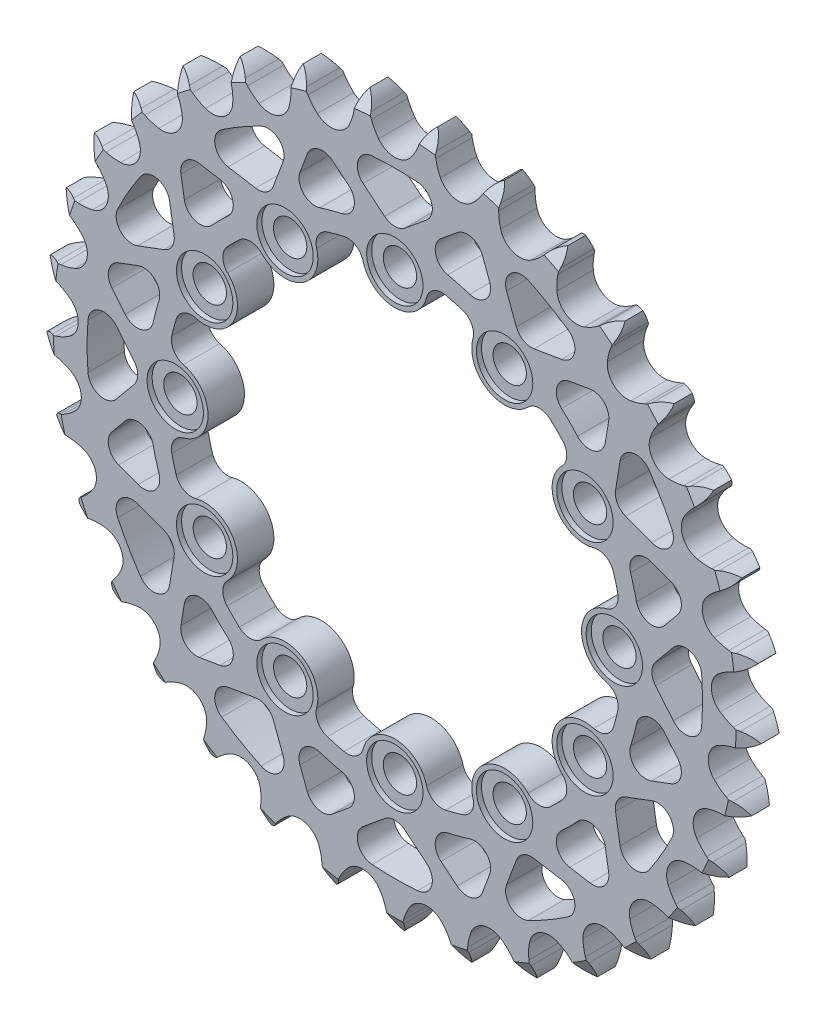
SolidWorks part; units mm, degrees
note: '?' marks a value the reader was unsure of. The reader was unsure of these and kept them because the rebuilt part matched: shared geometry of "Sketch12<3>".
material "7075-T6 (SN)"
ref_plane "Front Plane" through (0, 0, 0) normal (0, 0, 1) x (1, 0, 0)
ref_plane "Top Plane" through (0, 0, 0) normal (0, 1, 0) x (1, 0, 0)
ref_plane "Right Plane" through (0, 0, 0) normal (1, 0, 0) x (0, 0, -1)
sketch "Work Sketch" plane through (0, 0, 0) normal (0, 0, 1) x (1, 0, 0)
  line L0 (0, 0) -> (0, 160.4542) construction
  line L1 (-112.0919, 66.8027) -> (87.2579, 66.8027) construction
  line L2 (5.0834, 120.8822) -> (5.0834, 112.9699) construction
  line L3 (-12.8497, 70.6081) -> (16.7256, 70.6081) construction
  line L4 (5.0834, 70.6081) -> (-6.0658, 62.2619) construction
  line L5 (5.0834, 70.6081) -> (-4.6352, 66.9715) construction
  line L6 (-4.6352, 66.9715) -> (-6.998, 73.2861)
  line L7 (-11.5114, 65.7464) -> (-7.1525, 65.7464) construction
  line L8 (-11.0622, 124.7602) -> (-11.0622, 110.2345) construction
  line L9 (0, 0) -> (-4.0639, 42.5596) construction
  circle A0 centre (0, 0) radius 66.8027
  circle A1 centre (0, 66.8027) radius 4.0088
  arc A2 (-4.6352, 66.9715) -> (-3.2092, 64.4003) centre (5.0609, 70.6677) ccw
  circle A3 centre (-11.0622, 65.7464) radius 6.4488
  point P23 (-3.2092, 64.4003)
  dimension "D1" = 133.6054
  dimension "D8" = 10.3767
  dimension "D2" = 8.0177
  dimension "D3" = 5.0834
  dimension "D4" = 3.8054
  dimension "D5" = 36.818
  dimension "D6" = 16.303
  dimension "D7" = 10.3767
  dimension "D9" = 1.0563
  dimension "D10" = 11.0622
  dimension "D11" = 5.455
sketch "Teeth Sketch" plane through (0, 0, 0) normal (0, 0, 1) x (1, 0, 0)
  line L0 (5.0224, 68.0064) -> (4.6352, 66.9715)
  line L1 (-8.8439, 92.6176) -> (-5.6513, 59.1829) construction
  line L2 (0, 0) -> (-12.8498, 132.1321) construction
  line L3 (7.9387, 67.7279) -> (8.123, 66.6385)
  line L4 (19011.2087, -199094.3845) -> (-19015.2726, 199136.9441) construction
  line L5 (0, 146.3285) -> (0, 56.9858) construction
  line L6 (17.8019, 65.8269) -> (17.2258, 64.8841)
  line L7 (0, -200000) -> (0, 200160.4542) construction
  line L8 (20.6128, 65.0016) -> (20.5877, 63.897)
  line L9 (-4.6352, 66.9715) -> (-6.998, 73.2861) construction
  line L10 (43.2949, 52.6844) -> (42.861, 51.6682)
  line L11 (-5.0224, 68.0064) -> (-4.6352, 66.9715)
  line L12 (29.938, 61.2683) -> (29.1939, 60.4515)
  line L13 (32.5419, 59.9259) -> (32.3082, 58.846)
  line L14 (40.9921, 54.4953) -> (40.1069, 53.8341)
  line L15 (50.5647, 45.7527) -> (49.5703, 45.271)
  line L16 (52.4831, 43.5387) -> (51.8648, 42.623)
  line L17 (58.3096, 35.3565) -> (57.2421, 35.0716)
  line L18 (59.7744, 32.8194) -> (58.9939, 32.0373)
  line L19 (63.9472, 23.6824) -> (62.845, 23.6047)
  line L20 (64.9053, 20.9139) -> (63.9909, 20.2936)
  line L21 (67.2735, 11.1523) -> (66.1765, 11.2846)
  line L22 (67.6904, 8.2526) -> (66.6751, 7.8165)
  line L23 (68.1683, -1.7808) -> (67.1162, -1.4433)
  line L24 (68.0289, -4.7071) -> (66.9495, -4.9431)
  line L25 (66.5994, -14.6496) -> (65.6302, -14.119)
  line L26 (65.9088, -17.4966) -> (64.8042, -17.524)
  line L27 (62.6234, -26.9889) -> (61.7722, -26.2845)
  line L28 (61.4065, -29.6537) -> (60.3166, -29.4716)
  line L29 (56.3841, -38.3527) -> (55.6815, -37.4999)
  line L30 (54.6848, -40.739) -> (53.6491, -40.354)
  line L31 (48.1068, -48.3304) -> (47.5783, -47.3601)
  line L32 (45.9866, -50.352) -> (45.0425, -49.7779)
  line L33 (38.0909, -56.5613) -> (37.7556, -55.5085)
  line L34 (35.6264, -58.1451) -> (34.808, -57.4027)
  line L35 (26.6983, -62.7479) -> (26.5682, -61.6506)
  line L36 (23.9786, -63.8367) -> (23.3155, -62.9529)
  line L37 (14.3407, -66.6666) -> (14.4207, -65.5646)
  line L38 (11.4641, -67.221) -> (10.9802, -66.2277)
  line L39 (1.4648, -68.1759) -> (1.7519, -67.1089)
  line L40 (-1.4648, -68.1759) -> (-1.7519, -67.1089)
  line L41 (-11.4641, -67.221) -> (-10.9802, -66.2277)
  line L42 (-14.3407, -66.6666) -> (-14.4207, -65.5646)
  line L43 (-23.9786, -63.8367) -> (-23.3155, -62.9529)
  line L44 (-26.6983, -62.7479) -> (-26.5682, -61.6506)
  line L45 (-35.6264, -58.1451) -> (-34.808, -57.4027)
  line L46 (-38.0909, -56.5613) -> (-37.7556, -55.5085)
  line L47 (-45.9866, -50.352) -> (-45.0425, -49.7779)
  line L48 (-48.1068, -48.3304) -> (-47.5783, -47.3601)
  line L49 (-54.6848, -40.739) -> (-53.6491, -40.354)
  line L50 (-56.3841, -38.3527) -> (-55.6815, -37.4999)
  line L51 (-61.4065, -29.6537) -> (-60.3166, -29.4716)
  line L52 (-62.6234, -26.9889) -> (-61.7722, -26.2845)
  line L53 (-65.9088, -17.4966) -> (-64.8042, -17.524)
  line L54 (-66.5994, -14.6496) -> (-65.6302, -14.119)
  line L55 (-68.0289, -4.7071) -> (-66.9495, -4.9431)
  line L56 (-68.1683, -1.7808) -> (-67.1162, -1.4433)
  line L57 (-67.6904, 8.2526) -> (-66.6751, 7.8165)
  line L58 (-67.2735, 11.1523) -> (-66.1765, 11.2846)
  line L59 (-64.9053, 20.9139) -> (-63.9909, 20.2936)
  line L60 (-63.9472, 23.6824) -> (-62.845, 23.6047)
  line L61 (-59.7744, 32.8194) -> (-58.9939, 32.0373)
  line L62 (-58.3096, 35.3565) -> (-57.2421, 35.0716)
  line L63 (-52.4831, 43.5387) -> (-51.8648, 42.623)
  line L64 (-50.5647, 45.7527) -> (-49.5703, 45.271)
  line L65 (-43.2949, 52.6844) -> (-42.861, 51.6682)
  line L66 (-40.9921, 54.4953) -> (-40.1069, 53.8341)
  line L67 (-32.5419, 59.9259) -> (-32.3082, 58.846)
  line L68 (-29.938, 61.2683) -> (-29.1939, 60.4515)
  line L69 (-20.6128, 65.0016) -> (-20.5877, 63.897)
  line L70 (-17.8019, 65.8269) -> (-17.2258, 64.8841)
  line L71 (-7.9387, 67.7279) -> (-8.123, 66.6385)
  arc A0 (-6.8704, 70.647) -> (-5.0224, 68.0064) centre (-11.0622, 65.7464) cw
  circle A1 centre (-11.0622, 65.7464) radius 6.4488 construction
  arc A2 (-3.2092, 64.4003) -> (-4.6352, 66.9715) centre (5.0609, 70.6677) cw
  arc A3 (-4.6352, 66.9715) -> (-3.2092, 64.4003) centre (5.0609, 70.6677) ccw construction
  circle A4 centre (0, 66.8027) radius 4.0088 construction
  arc A5 (-3.2092, 64.4003) -> (3.2092, 64.4003) centre (0, 66.8027) ccw
  arc A6 (3.2092, 64.4003) -> (4.6352, 66.9715) centre (-5.0609, 70.6677) ccw
  arc A7 (6.8704, 70.647) -> (5.0224, 68.0064) centre (11.0622, 65.7464) ccw
  arc A8 (6.6238, 70.6705) -> (7.9387, 67.7279) centre (1.5803, 66.6518) cw
  arc A9 (9.0366, 63.8438) -> (8.123, 66.6385) centre (18.3434, 68.4328) cw
  arc A10 (9.0366, 63.8438) -> (15.3391, 62.6291) centre (12.6425, 65.5955) ccw
  arc A11 (15.3391, 62.6291) -> (17.2258, 64.8841) centre (8.4044, 70.3484) ccw
  arc A12 (20.1163, 68.0701) -> (17.8019, 65.8269) centre (23.3049, 62.4647) ccw
  arc A13 (19.8786, 68.1399) -> (20.6128, 65.0016) centre (14.1657, 65.1482) cw
  arc A14 (20.9558, 60.9799) -> (20.5877, 63.897) centre (30.9629, 63.7246) cw
  arc A15 (20.9558, 60.9799) -> (26.9145, 58.5944) centre (24.8281, 62.0175) ccw
  arc A16 (26.9145, 58.5944) -> (29.1939, 60.4515) centre (21.5661, 67.4865) ccw
  arc A17 (32.6351, 63.0329) -> (29.938, 61.2683) centre (34.7052, 56.9254) ccw
  arc A18 (32.4149, 63.1465) -> (32.5419, 59.9259) centre (26.2391, 61.29) cw
  arc A19 (32.1176, 55.912) -> (32.3082, 58.846) centre (42.4634, 56.7133) cw
  arc A20 (32.1176, 55.912) -> (37.5172, 52.4419) centre (36.1163, 56.198) ccw
  arc A21 (37.5172, 52.4419) -> (40.1069, 53.8341) centre (33.9483, 62.1856) ccw
  arc A22 (43.9744, 55.7176) -> (40.9921, 54.4953) centre (44.8513, 49.3287) ccw
  arc A23 (43.7796, 55.8708) -> (43.2949, 52.6844) centre (37.3641, 55.2167) cw
  arc A24 (42.1187, 48.8233) -> (42.861, 51.6682) centre (52.429, 47.6521) cw
  arc A25 (42.1187, 48.8233) -> (46.7639, 44.3941) centre (46.0991, 48.3474) ccw
  arc A26 (46.7639, 44.3941) -> (49.5703, 45.271) centre (45.1035, 54.637) ccw
  arc A27 (53.7244, 46.3885) -> (50.5647, 45.7527) centre (53.3763, 39.9491) ccw
  arc A28 (53.5621, 46.5757) -> (52.4831, 43.5387) centre (47.1387, 47.1476) cw
  arc A29 (50.5974, 39.97) -> (51.8648, 42.623) centre (60.4998, 36.8687) cw
  arc A30 (50.5974, 39.97) -> (54.3205, 34.7417) centre (54.4159, 38.7494) ccw
  arc A31 (54.3205, 34.7417) -> (57.2421, 35.0716) centre (54.6285, 45.1138) ccw
  arc A32 (61.5326, 35.3828) -> (58.3096, 35.3565) centre (59.9721, 29.1257) ccw
  arc A33 (61.4087, 35.5974) -> (59.7744, 32.8194) centre (55.2096, 37.3746) cw
  arc A34 (57.2474, 29.6721) -> (58.9939, 32.0373) centre (66.384, 24.7528) cw
  arc A35 (57.2474, 29.6721) -> (59.9137, 23.8336) centre (60.7659, 27.7508) ccw
  arc A36 (59.9137, 23.8336) -> (62.845, 23.6047) centre (62.1792, 33.96) ccw
  arc A37 (67.1168, 23.0983) -> (63.9472, 23.6824) centre (64.4004, 17.2495) ccw
  arc A38 (67.0358, 23.3324) -> (64.9053, 20.9139) centre (61.2851, 26.2507) cw
  arc A39 (61.8283, 18.3017) -> (63.9909, 20.2936) centre (69.8688, 11.7422) cw
  arc A40 (61.8283, 18.3017) -> (63.3416, 12.0642) centre (64.9196, 15.7493) ccw
  arc A41 (63.3416, 12.0642) -> (66.1765, 11.2846) centre (67.4825, 21.5788) ccw
  arc A42 (70.2753, 9.9789) -> (67.2735, 11.1523) centre (66.5011, 4.7499) ccw
  arc A43 (70.2401, 10.2242) -> (67.6904, 8.2526) centre (65.1456, 14.178) cw
  arc A44 (64.1746, 6.2699) -> (66.6751, 7.8165) centre (70.8284, -1.6927) cw
  arc A45 (64.1746, 6.2699) -> (64.48, -0.1413) centre (66.727, 3.1786) ccw
  arc A46 (64.48, -0.1413) -> (67.1162, -1.4433) centre (70.3468, 8.4177) ccw
  arc A47 (70.8939, -3.5011) -> (68.1683, -1.7808) centre (66.1983, -7.9213) ccw
  arc A48 (70.9057, -3.2536) -> (68.0289, -4.7071) centre (66.6515, 1.5929) cw
  arc A49 (64.2015, -5.9885) -> (66.9495, -4.9431) centre (69.2281, -15.0665) cw
  arc A50 (64.2015, -5.9885) -> (63.2881, -12.3417) centre (66.1227, -9.507) ccw
  arc A51 (63.2881, -12.3417) -> (65.6302, -14.119) centre (70.6686, -5.0476) ccw
  arc A52 (68.9501, -16.8546) -> (66.5994, -14.6496) centre (63.5029, -20.3063) ccw
  arc A53 (69.0085, -16.6138) -> (65.9088, -17.4966) centre (65.7485, -11.0498) cw
  arc A54 (61.908, -18.0305) -> (64.8042, -17.524) centre (65.1257, -27.8957) cw
  arc A55 (61.908, -18.0305) -> (59.8087, -24.096) centre (63.1286, -21.849) ccw
  arc A56 (59.8087, -24.096) -> (61.7722, -26.2845) centre (68.4363, -18.3305) ccw
  arc A57 (64.5144, -29.5989) -> (62.6234, -26.9889) centre (58.5123, -31.9573) ccw
  arc A58 (64.6173, -29.3735) -> (61.4065, -29.6537) centre (62.4691, -23.2931) cw
  arc A59 (57.3769, -29.4209) -> (60.3166, -29.4716) centre (58.6695, -39.7167) cw
  arc A60 (57.3769, -29.4209) -> (54.1677, -34.9794) centre (57.8528, -33.4013) ccw
  arc A61 (54.1677, -34.9794) -> (55.6815, -37.4999) centre (63.7305, -30.9509) ccw
  arc A62 (57.7469, -41.2734) -> (56.3841, -38.3527) centre (51.4069, -42.4533) ccw
  arc A63 (57.8906, -41.0716) -> (54.6848, -40.739) centre (56.932, -34.6945) cw
  arc A64 (50.7721, -39.7478) -> (53.6491, -40.354) centre (50.0928, -50.1023) cw
  arc A65 (50.7721, -39.7478) -> (46.5689, -44.5986) centre (50.4861, -43.7465) ccw
  arc A66 (46.5689, -44.5986) -> (47.5783, -47.3601) centre (56.7213, -42.4527) ccw
  arc A67 (48.8923, -51.4562) -> (48.1068, -48.3304) centre (42.4436, -51.415) ccw
  arc A68 (49.0716, -51.2853) -> (45.9866, -50.352) centre (49.3372, -44.842) cw
  arc A69 (42.3322, -48.6382) -> (45.0425, -49.7779) centre (39.7057, -58.677) cw
  arc A70 (42.3322, -48.6382) -> (37.287, -52.6059) centre (41.2947, -52.5105) ccw
  arc A71 (37.287, -52.6059) -> (37.7556, -55.5085) centre (47.662, -52.4201) ccw
  arc A72 (38.2706, -59.7793) -> (38.0909, -56.5613) centre (31.9463, -58.5183) ccw
  arc A73 (38.479, -59.6453) -> (35.6264, -58.1451) centre (39.9592, -53.3687) cw
  arc A74 (32.3624, -55.7707) -> (34.808, -57.4027) centre (27.8834, -65.131) cw
  arc A75 (32.3624, -55.7707) -> (26.6574, -58.7118) centre (30.6108, -59.3766) ccw
  arc A76 (26.6574, -58.7118) -> (26.5682, -61.6506) centre (36.8801, -60.4929) ccw
  arc A77 (26.2657, -65.9417) -> (26.6983, -62.7479) centre (20.2943, -63.5067) ccw
  arc A78 (26.4957, -65.8497) -> (23.9786, -63.8367) centre (29.137, -59.9666) cw
  arc A79 (21.2229, -60.8875) -> (23.3155, -62.9529) centre (15.0534, -69.2309) cw
  arc A80 (21.2229, -60.8875) -> (15.0644, -62.6958) centre (18.8205, -64.0967) ccw
  arc A81 (15.0644, -62.6958) -> (14.4207, -65.5646) centre (24.7653, -66.3793) ccw
  arc A82 (13.3114, -69.7209) -> (14.3407, -66.6666) centre (7.9088, -66.1998) ccw
  arc A83 (13.5547, -69.674) -> (11.4641, -67.221) centre (17.2617, -64.3972) cw
  arc A84 (9.3163, -63.8036) -> (10.9802, -66.2277) centre (1.6794, -70.8287) cw
  arc A85 (9.3163, -63.8036) -> (2.9269, -64.4137) centre (6.35, -66.5002) ccw
  arc A86 (2.9269, -64.4137) -> (1.7519, -67.1089) centre (11.7554, -69.8666) ccw
  arc A87 (-0.1239, -70.9802) -> (1.4648, -68.1759) centre (-4.7625, -66.5002) ccw
  arc A88 (0.1239, -70.9802) -> (-1.4648, -68.1759) centre (4.7625, -66.5002) cw
  arc A89 (-2.9269, -64.4137) -> (-1.7519, -67.1089) centre (-11.7554, -69.8666) cw
  arc A90 (-2.9269, -64.4137) -> (-9.3163, -63.8036) centre (-6.35, -66.5002) ccw
  arc A91 (-9.3163, -63.8036) -> (-10.9802, -66.2277) centre (-1.6794, -70.8287) ccw
  arc A92 (-13.5547, -69.674) -> (-11.4641, -67.221) centre (-17.2617, -64.3972) ccw
  arc A93 (-13.3114, -69.7209) -> (-14.3407, -66.6666) centre (-7.9088, -66.1998) cw
  arc A94 (-15.0644, -62.6958) -> (-14.4207, -65.5646) centre (-24.7653, -66.3793) cw
  arc A95 (-15.0644, -62.6958) -> (-21.2229, -60.8875) centre (-18.8205, -64.0967) ccw
  arc A96 (-21.2229, -60.8875) -> (-23.3155, -62.9529) centre (-15.0534, -69.2309) ccw
  arc A97 (-26.4957, -65.8497) -> (-23.9786, -63.8367) centre (-29.137, -59.9666) ccw
  arc A98 (-26.2657, -65.9417) -> (-26.6983, -62.7479) centre (-20.2943, -63.5067) cw
  arc A99 (-26.6574, -58.7118) -> (-26.5682, -61.6506) centre (-36.8801, -60.4929) cw
  arc A100 (-26.6574, -58.7118) -> (-32.3624, -55.7707) centre (-30.6108, -59.3766) ccw
  arc A101 (-32.3624, -55.7707) -> (-34.808, -57.4027) centre (-27.8834, -65.131) ccw
  arc A102 (-38.479, -59.6453) -> (-35.6264, -58.1451) centre (-39.9592, -53.3687) ccw
  arc A103 (-38.2706, -59.7793) -> (-38.0909, -56.5613) centre (-31.9463, -58.5183) cw
  arc A104 (-37.287, -52.6059) -> (-37.7556, -55.5085) centre (-47.662, -52.4201) cw
  arc A105 (-37.287, -52.6059) -> (-42.3322, -48.6382) centre (-41.2947, -52.5105) ccw
  arc A106 (-42.3322, -48.6382) -> (-45.0425, -49.7779) centre (-39.7057, -58.677) ccw
  arc A107 (-49.0716, -51.2853) -> (-45.9866, -50.352) centre (-49.3372, -44.842) ccw
  arc A108 (-48.8923, -51.4562) -> (-48.1068, -48.3304) centre (-42.4436, -51.415) cw
  arc A109 (-46.5689, -44.5986) -> (-47.5783, -47.3601) centre (-56.7213, -42.4527) cw
  arc A110 (-46.5689, -44.5986) -> (-50.7721, -39.7478) centre (-50.4861, -43.7465) ccw
  arc A111 (-50.7721, -39.7478) -> (-53.6491, -40.354) centre (-50.0928, -50.1023) ccw
  arc A112 (-57.8906, -41.0716) -> (-54.6848, -40.739) centre (-56.932, -34.6945) ccw
  arc A113 (-57.7469, -41.2734) -> (-56.3841, -38.3527) centre (-51.4069, -42.4533) cw
  arc A114 (-54.1677, -34.9794) -> (-55.6815, -37.4999) centre (-63.7305, -30.9509) cw
  arc A115 (-54.1677, -34.9794) -> (-57.3769, -29.4209) centre (-57.8528, -33.4013) ccw
  arc A116 (-57.3769, -29.4209) -> (-60.3166, -29.4716) centre (-58.6695, -39.7167) ccw
  arc A117 (-64.6173, -29.3735) -> (-61.4065, -29.6537) centre (-62.4691, -23.2931) ccw
  arc A118 (-64.5144, -29.5989) -> (-62.6234, -26.9889) centre (-58.5123, -31.9573) cw
  arc A119 (-59.8087, -24.096) -> (-61.7722, -26.2845) centre (-68.4363, -18.3305) cw
  arc A120 (-59.8087, -24.096) -> (-61.908, -18.0305) centre (-63.1286, -21.849) ccw
  arc A121 (-61.908, -18.0305) -> (-64.8042, -17.524) centre (-65.1257, -27.8957) ccw
  arc A122 (-69.0085, -16.6138) -> (-65.9088, -17.4966) centre (-65.7485, -11.0498) ccw
  arc A123 (-68.9501, -16.8546) -> (-66.5994, -14.6496) centre (-63.5029, -20.3063) cw
  arc A124 (-63.2881, -12.3417) -> (-65.6302, -14.119) centre (-70.6686, -5.0476) cw
  arc A125 (-63.2881, -12.3417) -> (-64.2015, -5.9885) centre (-66.1227, -9.507) ccw
  arc A126 (-64.2015, -5.9885) -> (-66.9495, -4.9431) centre (-69.2281, -15.0665) ccw
  arc A127 (-70.9057, -3.2536) -> (-68.0289, -4.7071) centre (-66.6515, 1.5929) ccw
  arc A128 (-70.8939, -3.5011) -> (-68.1683, -1.7808) centre (-66.1983, -7.9213) cw
  arc A129 (-64.48, -0.1413) -> (-67.1162, -1.4433) centre (-70.3468, 8.4177) cw
  arc A130 (-64.48, -0.1413) -> (-64.1746, 6.2699) centre (-66.727, 3.1786) ccw
  arc A131 (-64.1746, 6.2699) -> (-66.6751, 7.8165) centre (-70.8284, -1.6927) ccw
  arc A132 (-70.2401, 10.2242) -> (-67.6904, 8.2526) centre (-65.1456, 14.178) ccw
  arc A133 (-70.2753, 9.9789) -> (-67.2735, 11.1523) centre (-66.5011, 4.7499) cw
  arc A134 (-63.3416, 12.0642) -> (-66.1765, 11.2846) centre (-67.4825, 21.5788) cw
  arc A135 (-63.3416, 12.0642) -> (-61.8283, 18.3017) centre (-64.9196, 15.7493) ccw
  arc A136 (-61.8283, 18.3017) -> (-63.9909, 20.2936) centre (-69.8688, 11.7422) ccw
  arc A137 (-67.0358, 23.3324) -> (-64.9053, 20.9139) centre (-61.2851, 26.2507) ccw
  arc A138 (-67.1168, 23.0983) -> (-63.9472, 23.6824) centre (-64.4004, 17.2495) cw
  arc A139 (-59.9137, 23.8336) -> (-62.845, 23.6047) centre (-62.1792, 33.96) cw
  arc A140 (-59.9137, 23.8336) -> (-57.2474, 29.6721) centre (-60.7659, 27.7508) ccw
  arc A141 (-57.2474, 29.6721) -> (-58.9939, 32.0373) centre (-66.384, 24.7528) ccw
  arc A142 (-61.4087, 35.5974) -> (-59.7744, 32.8194) centre (-55.2096, 37.3746) ccw
  arc A143 (-61.5326, 35.3828) -> (-58.3096, 35.3565) centre (-59.9721, 29.1257) cw
  arc A144 (-54.3205, 34.7417) -> (-57.2421, 35.0716) centre (-54.6285, 45.1138) cw
  arc A145 (-54.3205, 34.7417) -> (-50.5974, 39.97) centre (-54.4159, 38.7494) ccw
  arc A146 (-50.5974, 39.97) -> (-51.8648, 42.623) centre (-60.4998, 36.8687) ccw
  arc A147 (-53.5621, 46.5757) -> (-52.4831, 43.5387) centre (-47.1387, 47.1476) ccw
  arc A148 (-53.7244, 46.3885) -> (-50.5647, 45.7527) centre (-53.3763, 39.9491) cw
  arc A149 (-46.7639, 44.3941) -> (-49.5703, 45.271) centre (-45.1035, 54.637) cw
  arc A150 (-46.7639, 44.3941) -> (-42.1187, 48.8233) centre (-46.0991, 48.3474) ccw
  arc A151 (-42.1187, 48.8233) -> (-42.861, 51.6682) centre (-52.429, 47.6521) ccw
  arc A152 (-43.7796, 55.8708) -> (-43.2949, 52.6844) centre (-37.3641, 55.2167) ccw
  arc A153 (-43.9744, 55.7176) -> (-40.9921, 54.4953) centre (-44.8513, 49.3287) cw
  arc A154 (-37.5172, 52.4419) -> (-40.1069, 53.8341) centre (-33.9483, 62.1856) cw
  arc A155 (-37.5172, 52.4419) -> (-32.1176, 55.912) centre (-36.1163, 56.198) ccw
  arc A156 (-32.1176, 55.912) -> (-32.3082, 58.846) centre (-42.4634, 56.7133) ccw
  arc A157 (-32.4149, 63.1465) -> (-32.5419, 59.9259) centre (-26.2391, 61.29) ccw
  arc A158 (-32.6351, 63.0329) -> (-29.938, 61.2683) centre (-34.7052, 56.9254) cw
  arc A159 (-26.9145, 58.5944) -> (-29.1939, 60.4515) centre (-21.5661, 67.4865) cw
  arc A160 (-26.9145, 58.5944) -> (-20.9558, 60.9799) centre (-24.8281, 62.0175) ccw
  arc A161 (-20.9558, 60.9799) -> (-20.5877, 63.897) centre (-30.9629, 63.7246) ccw
  arc A162 (-19.8786, 68.1399) -> (-20.6128, 65.0016) centre (-14.1657, 65.1482) ccw
  arc A163 (-20.1163, 68.0701) -> (-17.8019, 65.8269) centre (-23.3049, 62.4647) cw
  arc A164 (-15.3391, 62.6291) -> (-17.2258, 64.8841) centre (-8.4044, 70.3484) cw
  arc A165 (-15.3391, 62.6291) -> (-9.0366, 63.8438) centre (-12.6425, 65.5955) ccw
  arc A166 (-9.0366, 63.8438) -> (-8.123, 66.6385) centre (-18.3434, 68.4328) ccw
  arc A167 (-6.6238, 70.6705) -> (-7.9387, 67.7279) centre (-1.5803, 66.6518) ccw
  point P77 (0, 0)
  dimension "D1" = 5.455
  dimension "D2" = 5.555
  dimension "D3" = 33
extrude "Extrusion" add sketch "Teeth Sketch" along normal blind 7.2136
ref_axis "Axis2" through (0, 0, 38.9715) along (0, 0, -1)?
hole_wizard "M6 Clearance Hole1" positions "Sketch6" profile "Sketch7" hole size "M6" standard "ANSI Metric"
sketch "Sketch6" plane through (0, 0, 0) normal (0, 0, -1) x (-1, 0, 0)
  circle A0 centre (0, 0) radius 43.5
  point P0 (0, 43.5)
  dimension "D1" = 87
sketch "Sketch7" plane through (0, 43.5, 0) normal (1, 0, 0) x (0, 1, 0)
  line L0 (0, 0) -> (0, 19.2548)
  line L1 (0, 19.2548) -> (3.3, 17.272)
  line L2 (3.3, 17.272) -> (3.3, 0)
  line L5 (3.3, 0) -> (0, 0)
  line L10 (0, 19.2548) -> (-3.3, 17.272) construction
  line L11 (0, -6.35) -> (0, 107.95) construction
  dimension "Hole Dia." = 6.6
  dimension "Hole Depth" = 17.272
  dimension "Drill Angle" = 118
pattern_circular "CirPattern1" count 12 over 360 about axis through (0, 0, 0) along (0, 0, 1) of "M6 Clearance Hole1"
sketch "Sketch8" plane through (0, 0, 0) normal (0, 0, -1) x (-1, 0, 0)
  circle A0 centre (0, 0) radius 37
  dimension "D1" = 74
extrude "Cut-Extrude1" cut sketch "Sketch8" against normal through all both and the other way through all
ref_plane "Sprocket Center Plane" through (0, 0, 3.6068) normal (0, 0, 1) x (1, 0, 0)
sketch "Pitch Circle" plane through (0, 0, 3.6068) normal (0, 0, -1) x (-1, 0, 0)
  circle A0 centre (0, 0) radius 66.8027 construction
  dimension "D1" = 133.6054
ref_plane "Center Plane" through (0, 0, 3.6068) normal (0, 0, 1) x (1, 0, 0)
ref_axis "Axis1" through (0, 0, 7.2136) along (0, 0, -1)
sketch "Sketch5" plane through (0, 0, 0) normal (1, 0, 0) x (0, 0, -1)
  line L0 (-1.8288, -70.8482) -> (-5.3848, -70.8482)
  line L1 (-7.2136, -51.2753) -> (0, -51.2753) construction
  line L2 (-5.3848, -70.8482) -> (-5.3848, -67.6547)
  line L3 (-5.3848, -67.6547) -> (-7.2136, -67.6547)
  line L4 (-7.2136, -67.6547) -> (-5.3848, -70.8482)
  line L5 (-7.2136, -67.6547) -> (-7.2136, -70.8482)
  line L6 (-7.2136, -70.8482) -> (-5.3848, -70.8482)
  line L10 (-7.2136, -70.8482) -> (0, -70.8482) construction
  dimension "D1" = 3.556
  dimension "D2" = 3.1936
  dimension "D3" = 1.8288
revolve "Cut-Revolve1" cut sketch "Sketch5" angle 360 about axis through (0, 0, 7.2136) along (0, 0, -1)
mirror "Mirror1" about plane through (0, 0, 3.6068) normal (0, 0, 1) of "Cut-Revolve1"
sketch "Sketch10" plane through (0, 0, 0) normal (0, 0, 1) x (1, 0, 0)
  circle A0 centre (-43.5, 0) radius 5.588
  dimension "D1" = 11.176
extrude "Cut-Extrude2" cut sketch "Sketch10" against normal blind 1.016 from surface at 7.2136 starting at face at (-37, 0, 7.2136)
pattern_circular "CirPattern2" count 12 over 360 about axis through (0, 0, 0) along (0, 0, 1) of "Cut-Extrude2"
ref_plane "Half Plane" through (0, 0, 3.6068) normal (0, 0, 1) x (1, 0, 0)
sketch "Motor Shaft Sprocket Dimensions" plane through (0, 0, 3.6068) normal (0, 0, 1) x (1, 0, 0)
  line L0 (0, 0) -> (-177.8, 0)
  line L1 (-177.8, 0) -> (-177.8, 23.6982)
  line L2 (-180.2273, 51.0991) -> (-5.8945, 66.5421)
  line L3 (-187.3193, -2.1104) -> (-23.1174, -62.6753)
  line L4 (-5.8945, 66.5421) -> (0, 0)
  line L5 (0, 0) -> (-23.1174, -62.6753)
  circle A0 centre (-177.8, 23.6982) radius 27.5082
  circle A1 centre (0, 0) radius 66.8027 construction
  dimension "D3" = 55.0164
  dimension "D1" = 177.8
  dimension "D2" = 23.6982
  dimension "D4" = 205.308
sketch "Sketch12" plane through (0, 0, 0) normal (0, 0, 1) x (1, 0, 0)
  line L0 (-30.8788, 0) -> (49969.1212, 0) construction
  line L1 (-26.8339, 15.4926) -> (43274.4363, -24984.5074) construction
  line L2 (-31.6175, 8.4719) -> (48264.6738, -12932.4804) construction
  line L3 (-58.8828, 15.7776) -> (-48.8851, 3.6402)
  line L4 (-58.8828, 15.7776) -> (-44.1558, 21.29)
  line L5 (-59.7901, 11.8853) -> (-50, 0)
  line L6 (-59.7901, -11.8853) -> (-50, 0)
  line L7 (-44.1558, 21.29) -> (-48.8851, 3.6402) construction
  line L8 (-42.0363, 16.9329) -> (-44.871, 6.3538) construction
  circle A0 centre (-43.5, 0) radius 6.5
  circle A1 centre (0, 0) radius 37 construction
  circle A2 centre (0, 0) radius 60.96 construction
  circle A3 centre (-37.6721, 21.75) radius 6.5
  arc A4 (-37, 0) -> (-32.0429, 18.5) centre (0, 0) cw
  arc A5 (-59.7901, -11.8853) -> (-59.7901, 11.8853) centre (0, 0) cw
  arc A6 (-48.8851, 3.6402) -> (-44.1558, 21.29) centre (0, 0) cw
  arc A7 (-44.871, 6.3538) -> (-42.0363, 16.9329) centre (0, 0) cw
  point P17 (-35.7393, 9.5763)
  point P18 (-58.8828, 15.7776)
  dimension "D1" = 121.92
  dimension "D2" = 3.175
  dimension "D3" = 3.175
extrude "Cut-Extrude3" cut sketch "Sketch12" along normal through all contours A0 A4 A3 L4 L3 | L7 L4 L3
fillet "Fillet1" radius 3.175 5 edges at (-58.8828, 15.7776, 3.6068) (-44.871, 6.3538, 3.6068) (-42.0363, 16.9329, 3.6068) (-48.8851, 3.6402, 3.6068) (-44.1558, 21.29, 3.6068)
extrude "Cut-Extrude4" cut sketch "Sketch12<3>" along normal through all contours A5 L6 L5
sketch "Sketch12<3>" plane through (0, 0, 0) normal (0, 0, 1) x (1, 0, 0) same geometry as "Sketch12"
fillet "Fillet3" radius 3.175 3 edges at (-50, 0, 3.6068) (-59.7901, -11.8853, 3.6068) (-59.7901, 11.8853, 3.6068)
pattern_circular "CirPattern4" count 12 over 360 about axis through (0, 0, 0) along (0, 0, 1) of "Cut-Extrude3", "Cut-Extrude4", "Fillet1", "Fillet3"
equation "\"P\"= 0.500'//Chain Pitch"
equation "\"N\"= 33'//Number of Teeth"
equation "\"Dr\"= 5 / 16'//Roller Diameter"
equation "\"Ds\"= 1.0005 * \"Dr\" + 0.003'Seating Curve DIameter"
equation "\"R\"= \"Ds\" / 2"
equation "\"A\"= 35 + 60 / \"N\""
equation "\"B\"= 18 - 56 / \"N\""
equation "\"ac\"= 0.8 * \"Dr\""
equation "\"M\"= 0.8 * \"Dr\" * cos ( 35 + 60 / \"N\" )"
equation "\"T\"= 0.8 * \"Dr\" * sin ( 35 + 60 / \"N\" )"
equation "\"E\"= 1.3025 * \"Dr\" + 0.0015"
equation "\"Chordal Length of Arc xy\"= ( 2.605 * \"Dr\" + 0.003 ) * sin ( 9 - 28 / \"N\" )"
equation "\"yz\"= \"Dr\" * ( 1.4 * sin ( 17 - 64 / \"N\" ) - 0.8 * sin ( 18 - 56 / \"N\" ) )"
equation "\"ab\"= 1.4 * \"Dr\""
equation "\"W\"= 1.4 * \"Dr\" * cos ( 180 / \"N\" )"
equation "\"V\"= 1.4 * \"Dr\" * sin ( 180 / \"N\" )"
equation "\"F\"= \"Dr\" * ( 0.8 * cos ( 18 - 56 / \"N\" ) + 1.4 * cos ( 17 - 64 / \"N\" ) - 1.3025 )"
equation "\"H\"= sqr ( \"F\" ^ 2 - ( 1.4 * \"Dr\" - \"P\" / 2 ) ^ 2 )"
equation "\"S\"= \"P\" / 2 * cos ( 180 / \"N\" ) + \"H\" * sin ( 180 / \"N\" )"
equation "\"PD\"= \"P\" / ( sin ( 180 / \"N\" ) )"
equation "\"D1@Work Sketch\" = \"PD\""
equation "\"D3@Work Sketch\" = \"M\""
equation "\"D4@Work Sketch\" = \"T\""
equation "\"D5@Work Sketch\" = \"A\""
equation "\"D6@Work Sketch\" = \"B\""
equation "\"D7@Work Sketch\" = \"E\""
equation "\"D8@Work Sketch\" = \"E\""
equation "\"D9@Work Sketch\" = \"V\""
equation "\"D10@Work Sketch\" = \"W\""
equation "\"D2@Work Sketch\" = \"R\" * 2"
equation "\"D11@Work Sketch\" = 180 / \"N\""
equation "\"D2@Teeth Sketch\" = 180 / \"N\" + 0.1"
equation "\"D3@Teeth Sketch\" = \"N\""
equation "\"Edge Thickness\"=0.5"
equation "\"D1@Pitch Circle\"=\"PD\""
equation "\"ST\"= 0.284'//Sprocket Thickness"
